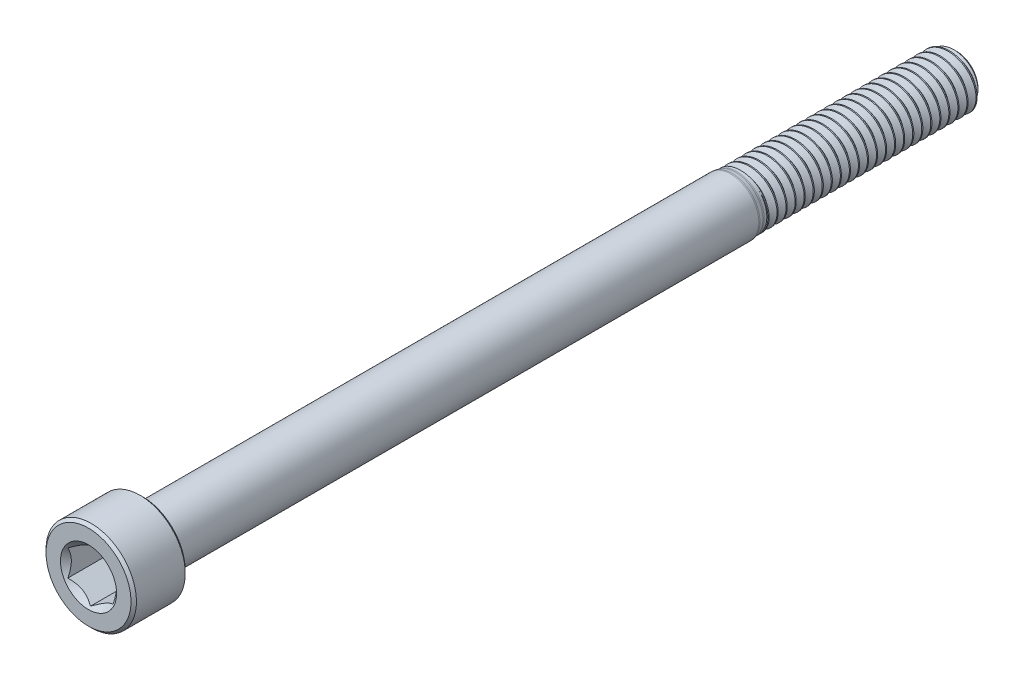
SolidWorks part; units mm, degrees
ref_plane "Front Plane" through (0, 0, 0) normal (0, 0, 1) x (1, 0, 0)
ref_plane "Top Plane" through (0, 0, 0) normal (0, 1, 0) x (1, 0, 0)
ref_plane "Right Plane" through (0, 0, 0) normal (1, 0, 0) x (0, 0, -1)
sketch "Sketch1" plane through (0, 0, 0) normal (1, 0, 0) x (0, 0, -1)
  line L0 (-48, 0) -> (48, 0) construction
  line L1 (48, 0) -> (48, 2.3505) construction
  line L2 (48, 2.3505) -> (47.3505, 3) construction
  line L3 (47.3505, 3) -> (47.25, 3) construction
  line L4 (47.25, 3) -> (-42, 3) construction
  line L5 (-42, 3) -> (-42, 5) construction
  line L6 (-42, 5) -> (-48, 5) construction
  line L7 (-48, 5) -> (-48, 0) construction
  line L8 (48, 2.3505) -> (48, 3) construction
  line L9 (47.9375, 3.1083) -> (48.4375, 2.2422) construction
  line L10 (48.4375, 2.2422) -> (48.9375, 3.1083) construction
  line L11 (48.9375, 3.1083) -> (47.9375, 3.1083) construction
  line L12 (48.4375, 3.1083) -> (48.4375, 3) construction
  line L13 (48.4375, 2.2422) -> (48.4375, 2.3505) construction
  line L14 (48.375, 2.3505) -> (48.5, 2.3505) construction
  line L15 (48, 3) -> (48.875, 3) construction
  line L16 (47.9688, 3.0541) -> (48.9063, 3.0541) construction
  line L17 (48, 0) -> (48, -3) construction
  line L18 (-42.3, 5) -> (-42, 4.7) construction
  line L19 (-47.7, 5) -> (-48, 4.7) construction
  line L20 (-42, 3) -> (-42, 0) construction
  line L21 (-42, 1.5) -> (-12, 1.5) construction
  line L22 (-12, 1.5) -> (18, 1.5) construction
  line L23 (18, 1.5) -> (48, 1.5) construction
  line L24 (-12, 1.5) -> (-12, 3) construction
  line L25 (-12, 3) -> (-12, 5) construction
  line L26 (18, 1.5) -> (18, 5) construction
  point P0 (-48, 2.5)
  point P3 (45.5, 3)
  point P4 (0, 0)
  point P18 (18, 3)
  point P22 (48.4375, 2.3505)
  point P24 (47.25, 3)
  point P25 (48.4375, 3)
  point P28 (48.4375, 3.0541)
  point P29 (45.5, -3)
  point P30 (-12, 3)
  point P31 (-45, 5)
  point P37 (-43.05, 5)
  point P38 (-47.55, 5)
  point P45 (-12, 1.5)
  point P46 (18, 1.5)
  point P49 (24, 3)
  dimension "D1" = 45
  dimension "D2" = 0.125
  dimension "D7" = 0.3
  dimension "D8" = 0.3
  dimension "D9" = 0.3
  dimension "D10" = 0.15
  dimension "D11" = 0.75
  dimension "Drive Size" = 5
  dimension "Head Diameter" = 10
  dimension "Head Height" = 6
  dimension "Thread Pitch" = 1
  dimension "Thread Dia" = 6
  dimension "Length" = 90
  dimension "D12" = 0.75
  dimension "D4" = 2.5
  dimension "Minimum Thread Length" = 24
  dimension "D3" = 66
sketch "Sketch2" plane through (0, 0, 0) normal (1, 0, 0) x (0, 0, -1)
  line L0 (-48, 0) -> (-48, 4.7)
  line L1 (-47.7, 5) -> (-42.3, 5)
  line L2 (-42, 4.7) -> (-42, 3.4083)
  line L4 (47.3505, 3) -> (48, 2.3505)
  line L5 (48, 2.3505) -> (48, 0)
  line L6 (-42, 5) -> (-48, 5) construction
  line L7 (48, 0) -> (-48, 0)
  line L8 (-47.7, 5) -> (-48, 4.7) construction
  line L10 (-47.7, 5) -> (-48, 4.7)
  line L14 (-42.3, 5) -> (-42, 4.7) construction
  line L16 (-42.3, 5) -> (-42, 4.7)
  line L17 (-42, 3) -> (-42, 5) construction
  line L18 (-41.7, 3.1083) -> (23.0069, 3.1083)
  line L19 (23.6989, 3) -> (47.3505, 3)
  line L20 (47.25, 3) -> (-42, 3) construction
  line L21 (23.1532, 3.0938) -> (23.5526, 3.0144)
  line L22 (48.9375, 3.1083) -> (47.9375, 3.1083) construction
  arc A1 (-42, 3.4083) -> (-41.7, 3.1083) centre (-41.7, 3.4083) ccw
  arc A2 (23.0069, 3.1083) -> (23.1532, 3.0938) centre (23.0069, 2.3583) cw
  arc A3 (23.5526, 3.0144) -> (23.6989, 3) centre (23.6989, 3.75) ccw
  point P39 (23.625, 3)
  dimension "D3" = 0.3
  dimension "D6" = 0.75
  dimension "D4" = 11.25
  dimension "D5" = 0.375
revolve "Revolve1" add sketch "Sketch2" angle 360 about L7
sketch "Sketch3" plane through (0, 0, 48) normal (0, 0, 1) x (1, 0, 0)
  line L1 (2.5, -1.4434) -> (2.5, 1.4434)
  line L2 (2.5, 1.4434) -> (0, 2.8868)
  line L3 (0, 2.8868) -> (-2.5, 1.4434)
  line L4 (-2.5, 1.4434) -> (-2.5, -1.4434)
  line L5 (-2.5, -1.4434) -> (0, -2.8868)
  line L6 (0, -2.8868) -> (2.5, -1.4434)
  circle A0 centre (0, 0) radius 2.5 construction
  circle A1 centre (0, 0) radius 5 construction
  circle A2 centre (0, 0) radius 5 construction
  circle A3 centre (0, 0) radius 2.8868 construction
  dimension "D1" = 5.7735
extrude "Cut-Extrude1" cut sketch "Sketch3" against normal offset from surface (5 mm away) 1 up to face at (-4.7, 0, 42)
sketch "Sketch4" plane through (0, 0, 48) normal (0, 0, 1) x (1, 0, 0)
  circle A0 centre (0, 0) radius 3.1033
  dimension "D1" = 6.2065
extrude "Cut-Extrude2" cut sketch "Sketch4" against normal up to vertex (3 mm away) draft 45 up to point (0, 5, 45)
sketch "Sketch11" plane through (0, 0, 0) normal (1, 0, 0) x (0, 0, -1)
  line L0 (-48, 0) -> (48, 0) construction
  line L1 (-48, 0) -> (48, 0) construction
  line L2 (-36.225, 0) -> (-36.225, 3) construction
  line L3 (47.25, 3) -> (-42, 3) construction
  line L4 (17.2319, 0) -> (17.2319, 3) construction
  point P2 (-36.225, 0)
  point P3 (17.2319, 0)
  dimension "D1" = 5.775
  dimension "D2" = 5.775
sketch "Sketch6" plane through (0, 0, -48) normal (0, 0, -1) x (-1, 0, 0)
  circle A0 centre (0, 0) radius 3
curve "Helix/Spiral1" pitch 1 height 25 radius 3 centre (0, 0, -48) axis (0, 0, 1) start towards (0, 1, 0)
sketch "Sketch10" plane through (0, 0, 0) normal (1, 0, 0) x (0, 0, -1)
  line L0 (24, -3) -> (24, 3)
  line L2 (-48, 0) -> (48, 0) construction
  point P3 (24, 0)
split "Split1" trim tools "Sketch10" bodies to split 106 resulting bodies 114 115
sketch "Sketch7" plane through (0, 0, 0) normal (1, 0, 0) x (0, 0, -1)
  line L0 (47.9688, 3.0541) -> (48.9063, 3.0541)
  line L1 (48.9063, 3.0541) -> (48.5, 2.3505)
  line L2 (48.5, 2.3505) -> (48.375, 2.3505)
  line L3 (48.375, 2.3505) -> (47.9688, 3.0541)
sweep "Cut-Sweep1" cut profiles "Sketch7" path "Helix/Spiral1" align with end faces yes
sketch "Sketch8" plane through (0, 0, 0) normal (1, 0, 0) x (0, 0, -1)
  line L0 (-42, 0) -> (-42, 3)
  line L2 (-42, 3) -> (24, 3)
  line L4 (24, 3) -> (25.7321, 0)
  line L5 (25.7321, 0) -> (-42, 0)
  line L6 (47.25, 3) -> (-42, 3) construction
  line L7 (-48, 0) -> (48, 0) construction
  dimension "D1" = 60
  dimension "D2" = 24
revolve "Revolve2" add sketch "Sketch8" angle 360 about L5
equation "\"D2@Sketch1\" = \"Thread Pitch@Sketch1\" / 8"
equation "\"D4@Helix/Spiral1\" = \"Thread Pitch@Sketch1\""
equation "\"D7@Sketch1\" = \"Head Height@Sketch1\" * .05"
equation "\"D8@Sketch1\"=\"D7@Sketch1\""
equation "\"D9@Sketch1\"=\"D7@Sketch1\""
equation "\"D10@Sketch1\"=\"D7@Sketch1\"/2"
equation "\"D11@Sketch1\"=\"D10@Sketch1\"*5"
equation "\"D4@Sketch1\"=\"Thread Pitch@Sketch1\"*2.5"
equation "\"D12@Sketch1\"=\"Thread Pitch@Sketch1\"*.75"
equation "\"D3@Helix/Spiral1\"=\"Minimum Thread Length@Sketch1\"+\"Thread Pitch@Sketch1\""
equation "\"D2@Sketch8\"=\"Minimum Thread Length@Sketch1\""
equation "\"D3@Sketch2\"=\"Thread Dia@Sketch1\"*0.05"
equation "\"D5@Sketch2\"=\"D12@Sketch1\"*0.5"
equation "\"D6@Sketch2\"=\"Thread Dia@Sketch1\"*0.125"
equation "\"D1@Sketch11\"=\"D3@Sketch1\"*0.0875"
equation "\"D2@Sketch11\"=\"D1@Sketch11\""
equation "\"D1@Sketch4\"=\"D1@Sketch3\"*1.075"
